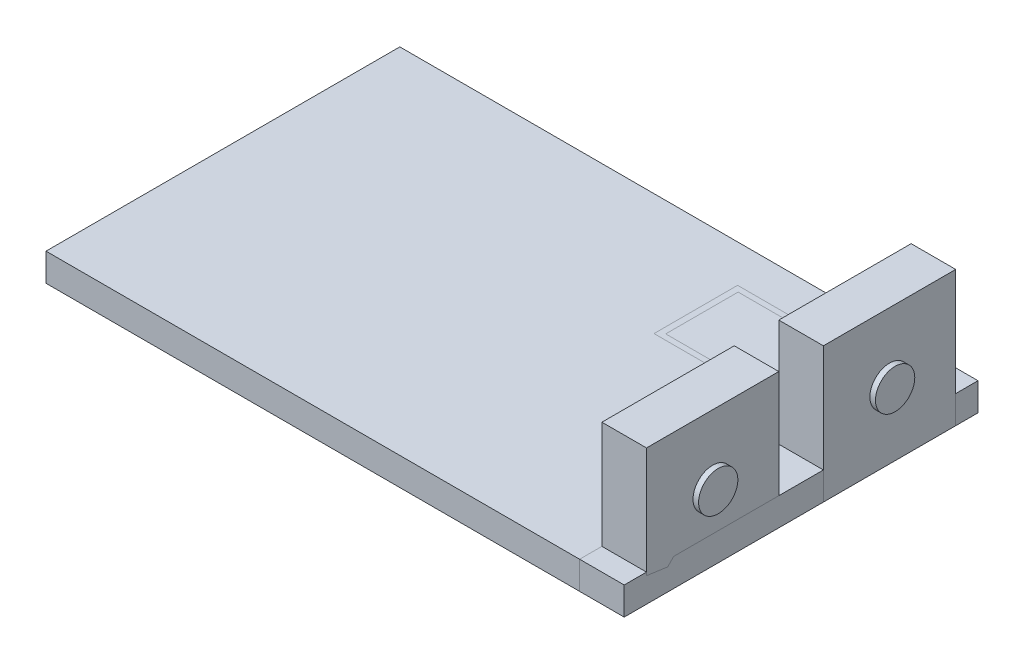
SolidWorks part; units mm, degrees
note: The reader was unsure of these and kept them because the rebuilt part matched: shared geometry of "Sketch1<3>", "Sketch1<4>", "Sketch1<5>", "Sketch1<6>".
ref_plane "Front Plane" through (0, 0, 0) normal (0, 0, 1) x (1, 0, 0)
ref_plane "Top Plane" through (0, 0, 0) normal (0, 1, 0) x (1, 0, 0)
ref_plane "Right Plane" through (0, 0, 0) normal (1, 0, 0) x (0, 0, -1)
sketch "Sketch1" plane through (0, 0, 0) normal (0, 1, 0) x (1, 0, 0)
  line L0 (43.4, 31.75) -> (43.4, -31.75)
  line L1 (-60.375, 31.75) -> (43.4, 31.75)
  line L2 (-60.375, 31.75) -> (-60.375, -31.75)
  line L3 (-60.375, -31.75) -> (43.4, -31.75)
  line L5 (35.4, 31.75) -> (35.4, -31.75)
  line L6 (35.4, -27.75) -> (43.4, -27.75)
  line L7 (35.4, 27.75) -> (43.4, 27.75)
  line L8 (7, 25) -> (28, 25)
  line L9 (39.4, 4) -> (35.4, 4)
  line L10 (43.4, 0) -> (43.4, 4)
  line L11 (43.4, 4) -> (39.4, 4)
  line L12 (7, 25) -> (7, 10)
  line L13 (39.4, -4) -> (43.4, -4)
  line L14 (39.4, -4) -> (35.4, -4)
  line L15 (7, 10) -> (28, 10)
  line L16 (28, 25) -> (28, 10)
  line L17 (8.1, 24) -> (26.9, 24)
  line L18 (8.1, 24) -> (8.1, 11)
  line L19 (8.1, 11) -> (26.9, 11)
  line L20 (26.9, 24) -> (26.9, 11)
extrude "Boss-Extrude1" add sketch "Sketch1" along normal blind 5
extrude "Boss-Extrude2" add sketch "Sketch1<3>" along normal blind 5 separate body
sketch "Sketch1<3>" plane through (0, 0, 0) normal (0, 1, 0) x (1, 0, 0) same geometry as "Sketch1"
extrude "Boss-Extrude3" add sketch "Sketch1<4>" along normal blind 24.3 separate body contours L11 L0 L7 L5 L9 | L13 L14 L5 L6 L0
sketch "Sketch1<4>" plane through (0, 0, 0) normal (0, 1, 0) x (1, 0, 0) same geometry as "Sketch1"
extrude "Boss-Extrude4" add sketch "Sketch1<5>" along normal blind 0.5 from offset 4.5 separate body contours L20 L17 L18 L19
sketch "Sketch1<5>" plane through (0, 0, 0) normal (0, 1, 0) x (1, 0, 0) same geometry as "Sketch1"
extrude "Boss-Extrude5" add sketch "Sketch1<6>" along normal blind 2 from offset 3 separate body contours L16 L8 L12 L15 L17 L20 L19 L18
sketch "Sketch1<6>" plane through (0, 0, 0) normal (0, 1, 0) x (1, 0, 0) same geometry as "Sketch1"
sketch "Sketch2" plane through (43.4, 0, 0) normal (1, 0, 0) x (0, 0, -1)
  circle A0 centre (15.875, 12.15) radius 3.528
  circle A1 centre (-15.875, 12.15) radius 3.5246
extrude "Boss-Extrude6" add sketch "Sketch2" along normal blind 1 separate body
